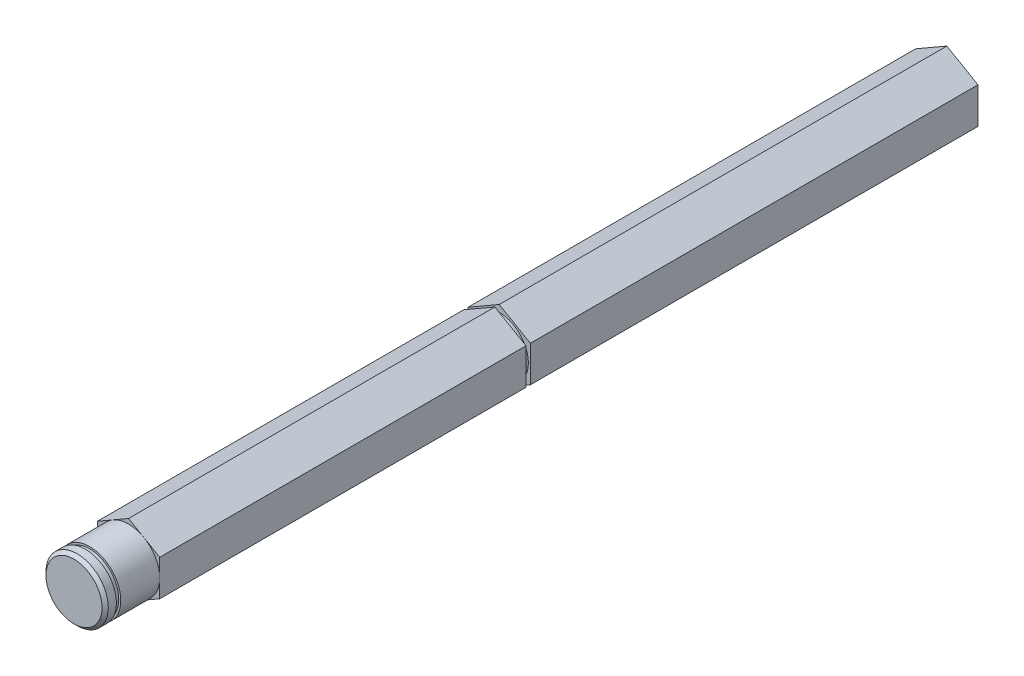
SolidWorks part; units mm, degrees
ref_plane "Front Plane" through (0, 0, 0) normal (0, 0, 1) x (1, 0, 0)
ref_plane "Top Plane" through (0, 0, 0) normal (0, 1, 0) x (1, 0, 0)
ref_plane "Right Plane" through (0, 0, 0) normal (1, 0, 0) x (0, 0, -1)
sketch "Sketch1" plane through (0, 0, 0) normal (0, 0, 1) x (1, 0, 0)
  line L1 (0, 7.3323) -> (-6.35, 3.6662)
  line L2 (-6.35, 3.6662) -> (-6.35, -3.6662)
  line L3 (-6.35, -3.6662) -> (0, -7.3323)
  line L4 (0, -7.3323) -> (6.35, -3.6662)
  line L5 (6.35, -3.6662) -> (6.35, 3.6662)
  line L6 (6.35, 3.6662) -> (0, 7.3323)
  circle A0 centre (0, 0) radius 6.35 construction
  dimension "D1" = 12.7
extrude "Boss-Extrude1" add sketch "Sketch1" along normal blind 177.8
sketch "Sketch2" plane through (0, 0, 177.8) normal (0, 0, 1) x (1, 0, 0)
  circle A0 centre (0, 0) radius 6.35
  circle A1 centre (0, 0) radius 7.3323
extrude "Cut-Extrude1" cut sketch "Sketch2" against normal blind 11.1125
sketch "Sketch3" plane through (0, 0, 0) normal (1, 0, 0) x (0, 0, -1)
  line L0 (-177.8, 0) -> (0, 0) construction
  line L1 (-177.8, 6.35) -> (-177.8, -6.35) construction
  line L2 (-166.6875, 6.35) -> (-177.8, 6.35) construction
  line L3 (-175.514, 6.35) -> (-174.625, 6.35)
  line L4 (-175.514, 6.35) -> (-175.514, 5.9436)
  line L5 (-175.514, 5.9436) -> (-174.625, 5.9436)
  line L6 (-174.625, 6.35) -> (-174.625, 5.9436)
  line L7 (-177.8, 6.35) -> (0, 6.35) construction
  line L8 (0, 3.6662) -> (0, 7.3323) construction
  line L10 (-92.075, 8.9817) -> (-91.186, 8.9817)
  line L11 (-92.075, 8.9817) -> (-92.075, 5.9436)
  line L12 (-92.075, 5.9436) -> (-91.186, 5.9436)
  line L13 (-91.186, 8.9817) -> (-91.186, 5.9436)
  dimension "D1" = 0.889
  dimension "D2" = 3.175
  dimension "D3" = 5.9436
  dimension "D4" = 0.889
  dimension "D5" = 82.55
revolve "Cut-Revolve1" cut sketch "Sketch3" angle 360 about L0
chamfer "Chamfer1" distance 0.635 angle 45 1 edges at (6.35, 0, 177.8)
equation "\"D3@Sketch3\"=0.468/2"
